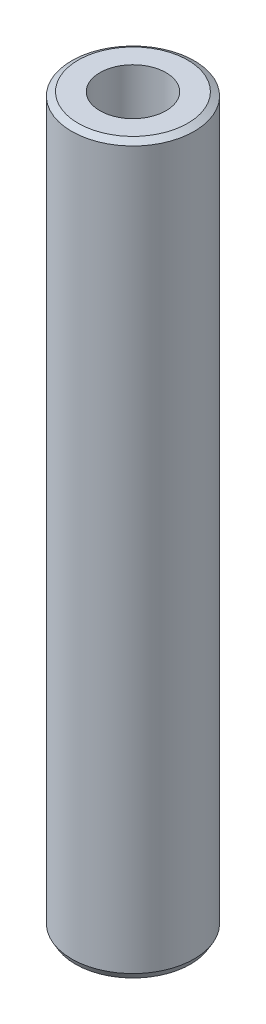
SolidWorks part; units mm, degrees
ref_plane "Front Plane" through (0, 0, 0) normal (0, 0, 1) x (1, 0, 0)
ref_plane "Top Plane" through (0, 0, 0) normal (0, 1, 0) x (1, 0, 0)
ref_plane "Right Plane" through (0, 0, 0) normal (1, 0, 0) x (0, 0, -1)
sketch "Sketch1" plane through (0, 0, 0) normal (0, 1, 0) x (1, 0, 0)
  circle A0 centre (0, 0) radius 5
  dimension "SHAFT_OD" = 10
extrude "Boss-Extrude1" add sketch "Sketch1" along normal blind 59.3319
sketch "Sketch2" plane through (0, 0, 0) normal (0, 1, 0) x (1, 0, 0)
  circle A0 centre (0, 0) radius 2.6977
  dimension "BORE_D" = 5.3954
extrude "Cut-Extrude1" cut sketch "Sketch2" along normal through all
chamfer "Chamfer1" distance 0.3052 angle 60 2 edges at (0, 59.3319, 5) (0, 0, 5) first distance on face at (0, 59.3319, 5) first distance on face at (0, 0, 2.6977)
